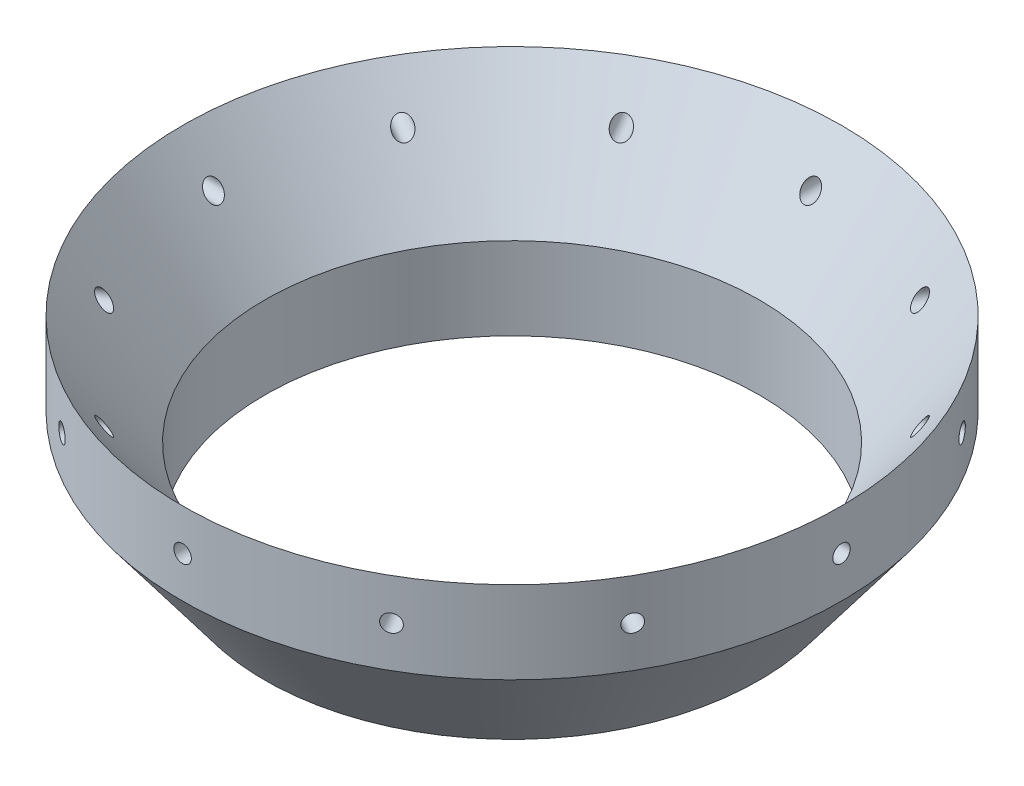
SolidWorks part; units mm, degrees
material "2024-T3"
ref_plane "Front Plane" through (0, 0, 0) normal (0, 0, 1) x (1, 0, 0)
ref_plane "Top Plane" through (0, 0, 0) normal (0, 1, 0) x (1, 0, 0)
ref_plane "Right Plane" through (0, 0, 0) normal (1, 0, 0) x (0, 0, -1)
sketch "Sketch1" plane through (0, 0, 0) normal (0, 0, 1) x (1, 0, 0)
  line L0 (0, 0) -> (0, 220.7687) construction
  line L1 (-57.15, 199.306) -> (-57.15, 218.356)
  line L2 (-57.15, 218.356) -> (-76.2, 243.756)
  line L3 (-76.2, 243.756) -> (-76.2, 224.706)
  line L4 (-76.2, 224.706) -> (-57.15, 199.306)
  dimension "D1" = 57.15
  dimension "D2" = 76.2
  dimension "D3" = 25.4
  dimension "D4" = 19.05
  dimension "D5" = 19.05
revolve "Revolve1" add sketch "Sketch1" angle 360 about L0
sketch "Sketch2" plane through (0, 0, 0) normal (0, 0, 1) x (1, 0, 0)
  line L0 (0, 235.8035) -> (0, 187.481) construction
  line L1 (76.2, 224.706) -> (-76.2, 224.706) construction
  circle A0 centre (0, 234.231) radius 2.0193
  dimension "D1" = 9.525
  dimension "D2" = 4.0386
extrude "Cut-Extrude1" cut sketch "Sketch2" against normal through all
ref_axis "Axis1" through (0, 235.8035, 0) along (0, -1, 0)
pattern_circular "CirPattern1" count 12 over 360 about axis through (0, 235.8035, 0) along (0, -1, 0) of "Cut-Extrude1"
